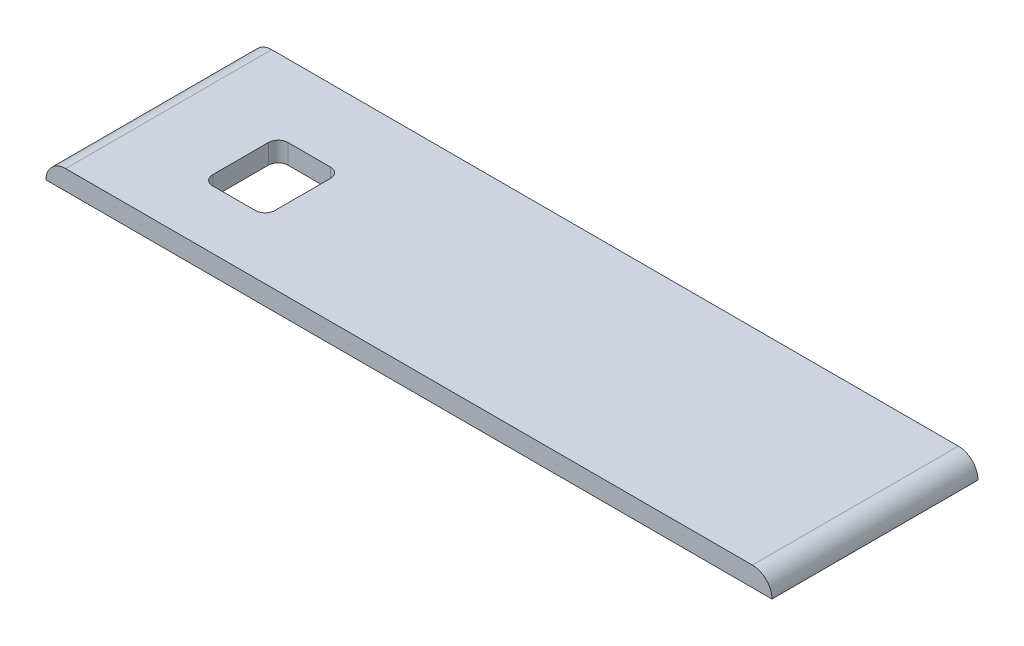
SolidWorks part; units mm, degrees
ref_plane "Спереди" through (0, 0, 0) normal (0, 0, 1) x (1, 0, 0)
ref_plane "Сверху" through (0, 0, 0) normal (0, 1, 0) x (1, 0, 0)
ref_plane "Справа" through (0, 0, 0) normal (1, 0, 0) x (0, 0, -1)
other "Configuration Table"
sketch "Эскиз1" plane through (0, 0, 0) normal (0, 1, 0) x (1, 0, 0)
  line L1 (-2, -31.5) -> (109, -31.5)
  line L2 (-2, -31.5) -> (-2, 0)
  line L3 (-2, 0) -> (109, 0)
  line L4 (109, -31.5) -> (109, 0)
  line L5 (13.05, -22.55) -> (22.55, -22.55)
  line L6 (13.05, -22.55) -> (13.05, -11.05)
  line L7 (13.05, -11.05) -> (22.55, -11.05)
  line L8 (22.55, -22.55) -> (22.55, -11.05)
extrude "Бобышка-Вытянуть1" add sketch "Эскиз1" along normal blind 3
fillet "tool_D3_R1p5_power_corners" radius 1.5 4 edges at (13.05, 1.5, 11.05) (22.55, 1.5, 11.05) (22.55, 1.5, 22.55) (13.05, 1.5, 22.55) tangent propagation no
fillet "tool_D3_R3_rear_outer_corners" radius 3 2 edges at (-2, 3, 15.75) (109, 3, 15.75)
